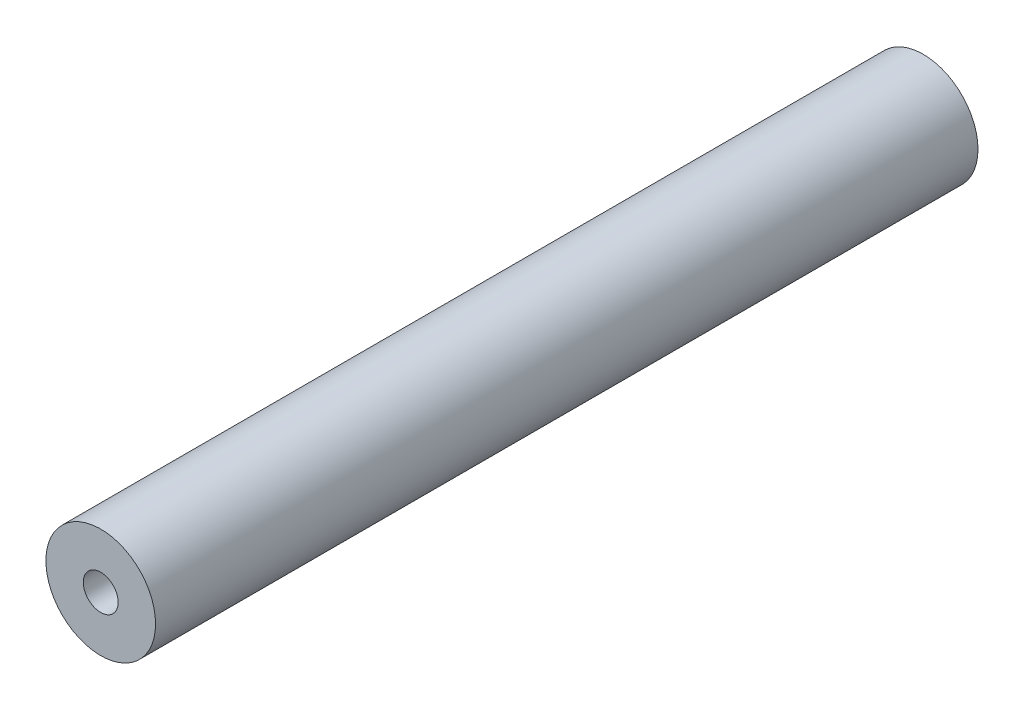
SolidWorks part; units mm, degrees
ref_plane "Front Plane" through (0, 0, 0) normal (0, 0, 1) x (1, 0, 0)
ref_plane "Top Plane" through (0, 0, 0) normal (0, 1, 0) x (1, 0, 0)
ref_plane "Right Plane" through (0, 0, 0) normal (1, 0, 0) x (0, 0, -1)
sketch "Sketch1" plane through (0, 0, 0) normal (0, 0, 1) x (1, 0, 0)
  circle A1 centre (0, 0) radius 6.35
  dimension "D2" = 12.7
extrude "Boss-Extrude1" add sketch "Sketch1" along normal mid plane 95.25 contours A1 region at (0, 0, 0)
hole_wizard "#10-32 Tapped Hole1" positions "3DSketch1" profile "Sketch2" tap size "#10-32" standard "ANSI Inch"
sketch3d "3DSketch1"
  line L0 (0, 0, 47.625) -> (0, 0, -47.625) construction
  point P0 (0, 0, 47.625)
  point P4 (0, 0, -47.625)
sketch "Sketch2" plane through (0, 0, 47.625) normal (1, 0, 0) x (0, -1, 0)
  line L0 (0, 0) -> (0, 13.2428)
  line L1 (0, 13.2428) -> (2.0193, 12.0294)
  line L2 (2.0193, 12.0294) -> (2.0193, 0)
  line L5 (2.0193, 0) -> (0, 0)
  line L10 (0, 13.2428) -> (-2.0193, 12.0294) construction
  line L11 (0, -6.35) -> (0, 107.95) construction
  dimension "Tap Drill Dia." = 4.0386
  dimension "Tap Drill Depth" = 12.0294
  dimension "Drill Angle" = 118
cosmetic thread "Hole Thread1" parameters "D1"=9.652, "D2"=4.826
cosmetic thread "Hole Thread2" parameters "D1"=9.652, "D2"=4.826
